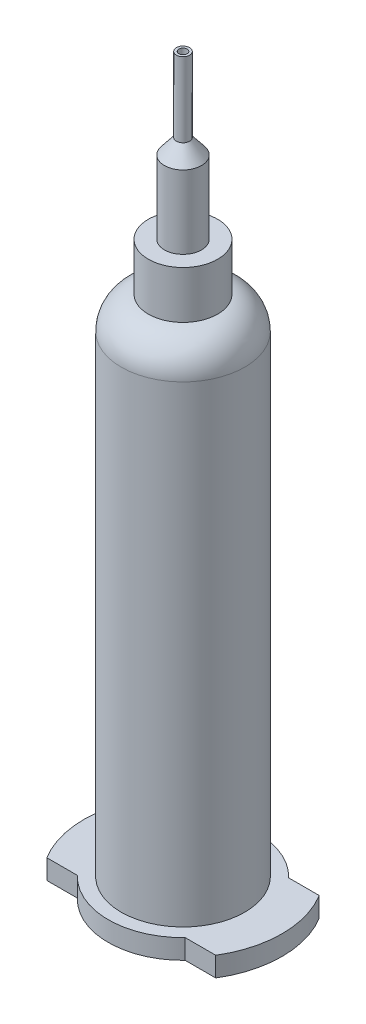
SolidWorks part; units mm, degrees
ref_plane "Front Plane" through (0, 0, 0) normal (0, 0, 1) x (1, 0, 0)
ref_plane "Top Plane" through (0, 0, 0) normal (0, 1, 0) x (1, 0, 0)
ref_plane "Right Plane" through (0, 0, 0) normal (1, 0, 0) x (0, 0, -1)
ref_axis "Axis1" through (-33.0333, 0, 0) along (1, 0, 0)
ref_axis "Axis2" through (0, 24.5224, 0) along (0, -1, 0)
ref_axis "Axis3" through (0, 0, -52.9538) along (0, 0, 1)
sketch "Sketch2" plane through (0, 0, 0) normal (0, 0, 1) x (1, 0, 0)
  line L8 (0, 55.88) -> (0, -55.88)
  line L9 (0, 55.88) -> (1, 55.88)
  line L10 (1, 55.88) -> (1, 44.53)
  line L11 (1, 44.53) -> (2.825, 42.2448)
  line L12 (2.825, 42.2448) -> (2.825, 31.12)
  line L13 (2.825, 31.12) -> (5.275, 31.12)
  line L14 (5.275, 31.12) -> (5.275, 23.88)
  line L15 (5.275, 23.88) -> (9.4, 23.88)
  line L16 (9.4, 23.88) -> (9.4, -52.88)
  line L17 (9.4, -52.88) -> (15.075, -52.88)
  line L18 (15.075, -52.88) -> (15.075, -55.88)
  line L19 (15.075, -55.88) -> (0, -55.88)
  point P2 (0, 0)
  point P4 (2.825, 52.2782)
  point P15 (2.825, 42.2448)
  point P16 (0, 0)
  point P17 (0, 0)
  dimension "D2" = 1
  dimension "D3" = 11.35
  dimension "D4" = 2.825
  dimension "D5" = 5.275
  dimension "D6" = 9.4
  dimension "D7" = 32
  dimension "D8" = 24.76
  dimension "D9" = 3
  dimension "D10" = 15.075
  dimension "D11" = 76.76
revolve "Revolve1" add sketch "Sketch2" angle 360 about axis through (0, 24.5224, 0) along (0, -1, 0) region at (4.5621, -11.6886, 0)
fillet "Fillet1" radius 5 1 edges at (0, 23.88, 9.4)
sketch "Sketch3" plane through (0, -52.88, 0) normal (0, 1, 0) x (1, 0, 0)
  line L0 (-12.8546, 7.875) -> (-8.2082, 7.875)
  line L1 (8.2082, 7.875) -> (12.8546, 7.875)
  line L2 (-111.883, 0) -> (111.883, 0) construction
  line L3 (-12.8546, -7.875) -> (-8.2082, -7.875)
  line L4 (8.2082, -7.875) -> (12.8546, -7.875)
  circle A0 centre (0, 0) radius 15.075 construction
  arc A1 (-8.2082, 7.875) -> (8.2082, 7.875) centre (0, 0) cw
  arc A2 (-12.8546, 7.875) -> (12.8546, 7.875) centre (0, 0) cw
  arc A3 (-8.2082, -7.875) -> (8.2082, -7.875) centre (0, 0) ccw
  arc A4 (-12.8546, -7.875) -> (12.8546, -7.875) centre (0, 0) ccw
  dimension "D2" = 11.375
  dimension "D1" = 15.75
extrude "Cut-Extrude1" cut sketch "Sketch3" against normal up to surface (3 mm away) up to face at (0, -55.88, 15.075)
sketch "Sketch4" plane through (0, -55.88, 0) normal (0, -1, 0) x (1, 0, 0)
  circle A0 centre (0, 0) radius 7.925
  dimension "D1" = 15.85
extrude "Cut-Extrude2" cut sketch "Sketch4" against normal blind 74
sketch "Sketch5" plane through (0, 55.88, 0) normal (0, 1, 0) x (1, 0, 0)
  circle A0 centre (0, 0) radius 0.6274
extrude "Cut-Extrude3" cut sketch "Sketch5" against normal blind 41
fillet "Fillet3" radius 10 1 edges at (0, 18.12, -0.6274)
ref_plane "Plane1" through (0, 18.12, 0) normal (0, 1, 0) x (1, 0, 0)
sketch "Sketch6" plane through (0, 18.12, 0) normal (0, 1, 0) x (1, 0, 0)
  circle A0 centre (0, 0) radius 7.925
  circle A1 centre (0, 0) radius 7.925 construction
extrude "Boss-Extrude2" add sketch "Sketch6" against normal blind 15 separate body
